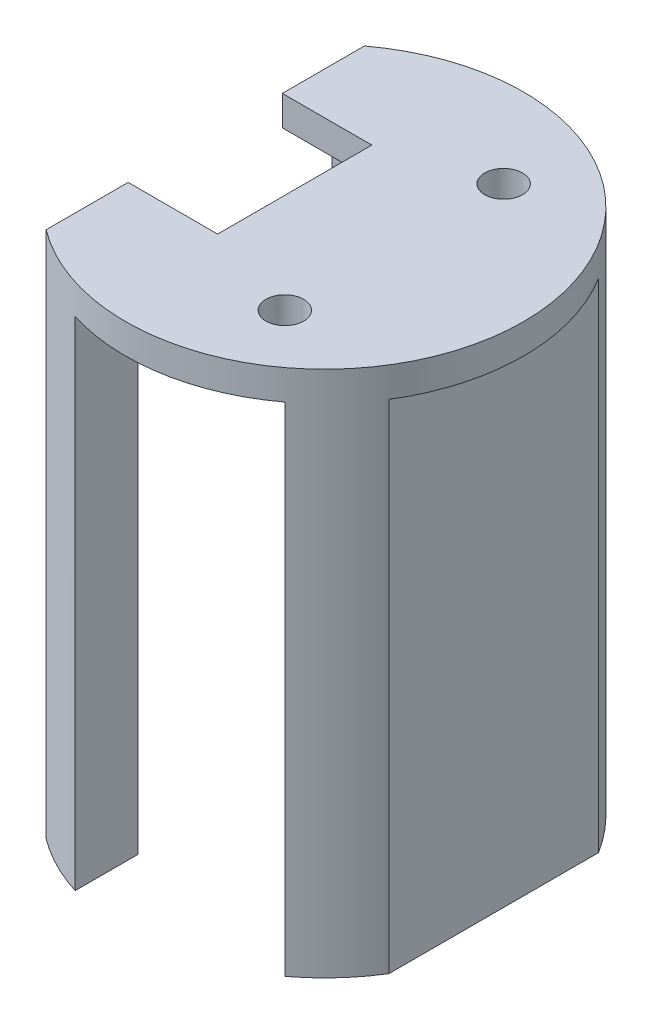
SolidWorks part; units mm, degrees
ref_plane "Front Plane" through (0, 0, 0) normal (0, 0, 1) x (1, 0, 0)
ref_plane "Top Plane" through (0, 0, 0) normal (0, 1, 0) x (1, 0, 0)
ref_plane "Right Plane" through (0, 0, 0) normal (1, 0, 0) x (0, 0, -1)
sketch "Sketch2" plane through (0, 0, 0) normal (0, 1, 0) x (1, 0, 0)
  line L0 (-3.81, 25.1126) -> (-3.81, -25.1126) construction
  line L1 (-15.24, -20.32) -> (-15.24, -9.8425)
  line L2 (-20.6326, -9.8425) -> (16.7847, -9.8425) construction
  line L3 (-15.24, -9.8425) -> (-3.81, -9.8425)
  line L4 (-3.81, -9.8425) -> (-3.81, 9.8425)
  line L5 (16.7847, 9.8425) -> (-20.6326, 9.8425) construction
  line L6 (-3.81, 9.8425) -> (-15.24, 9.8425)
  line L7 (-15.24, 9.8425) -> (-15.24, 20.32)
  line L8 (-15.24, -20.32) -> (-15.24, 20.32) construction
  circle A2 centre (0, 0) radius 25.4 construction
  arc A3 (-15.24, -20.32) -> (-15.24, 20.32) centre (0, 0) ccw
  dimension "D1" = 3.81
  dimension "D2" = 15.24
extrude "plate" add sketch "Sketch2" along normal blind 3.81
sketch "Sketch15" plane through (0, 0, 0) normal (0, -1, 0) x (1, 0, 0)
  circle A1 centre (8.89, 13.97) radius 2.413
  circle A2 centre (8.89, 13.97) radius 2.413 construction
  circle A3 centre (8.89, -13.97) radius 2.413
  circle A4 centre (8.89, -13.97) radius 2.413 construction
extrude "boltholes" cut sketch "Sketch15" against normal up to next
sketch "Sketch16" plane through (0, 0, 0) normal (0, -1, 0) x (1, 0, 0)
  line L0 (-15.24, 16.1925) -> (-7.62, 16.1925)
  line L1 (-15.24, 9.8425) -> (-15.24, 20.32) construction
  line L2 (-7.62, 16.1925) -> (-7.62, 24.2301)
  line L3 (-15.24, 16.1925) -> (-15.24, 20.32)
  line L4 (-3.81, 9.8425) -> (-15.24, 9.8425) construction
  line L6 (15.24, 20.32) -> (15.24, -20.32)
  line L7 (21.59, 13.3803) -> (21.59, -13.3803)
  line L8 (-15.24, -20.32) -> (-15.24, -16.1925)
  line L9 (-15.24, -20.32) -> (-15.24, -9.8425) construction
  line L10 (-15.24, -16.1925) -> (-7.62, -16.1925)
  line L11 (-7.62, -16.1925) -> (-7.62, -24.2301)
  arc A0 (-15.24, -20.32) -> (-15.24, 20.32) centre (0, 0) ccw construction
  arc A1 (-15.24, 20.32) -> (-7.62, 24.2301) centre (0, 0) cw
  arc A2 (15.24, 20.32) -> (21.59, 13.3803) centre (0, 0) cw
  arc A3 (15.24, -20.32) -> (21.59, -13.3803) centre (0, 0) ccw
  arc A4 (-15.24, -20.32) -> (-7.62, -24.2301) centre (0, 0) ccw
  point P26 (-6.9544, -24.4294)
  dimension "D1" = 6.35
  dimension "D3" = 6.35
  dimension "D4" = 15.24
  dimension "D2" = 7.62
extrude "Boss-Extrude1" add sketch "Sketch16" along normal blind 63.5
